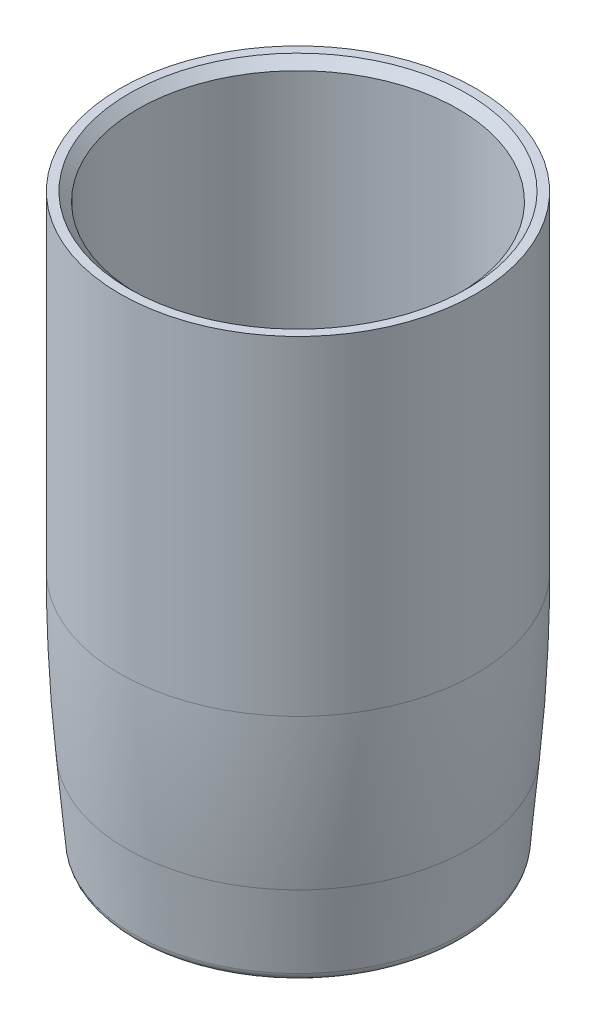
SolidWorks part; units mm, degrees
ref_plane "Front Plane" through (0, 0, 0) normal (0, 0, 1) x (1, 0, 0)
ref_plane "Top Plane" through (0, 0, 0) normal (0, 1, 0) x (1, 0, 0)
ref_plane "Right Plane" through (0, 0, 0) normal (1, 0, 0) x (0, 0, -1)
sketch "Sketch1" plane through (0, 0, 0) normal (0, 1, 0) x (1, 0, 0)
  circle A0 centre (0, 0) radius 5
  circle A1 centre (0, 0) radius 10
  dimension "D1" = 10
  dimension "D2" = 20
extrude "Boss-Extrude1" add sketch "Sketch1" along normal blind 2
sketch "Sketch2" plane through (0, 2, 0) normal (0, 1, 0) x (1, 0, 0)
  circle A0 centre (0, 0) radius 9
  circle A1 centre (0, 0) radius 10
  dimension "D1" = 18
extrude "Boss-Extrude2" add sketch "Sketch2" along normal blind 30
chamfer "Chamfer1" distance 0.8 angle 85 1 edges at (0, 0, 10) first distance on face at (0, 0, 10)
chamfer "Chamfer2" distance 0.5 angle 45 1 edges at (0, 32, 9)
fillet "Fillet1" radius 0.5 1 edges at (0, 0, 9.2)
fillet "Fillet2" radius 100 1 edges at (0, 9.144, 10)
chamfer "Chamfer3" distance 0.5 angle 45 1 edges at (0, 2, 5)
